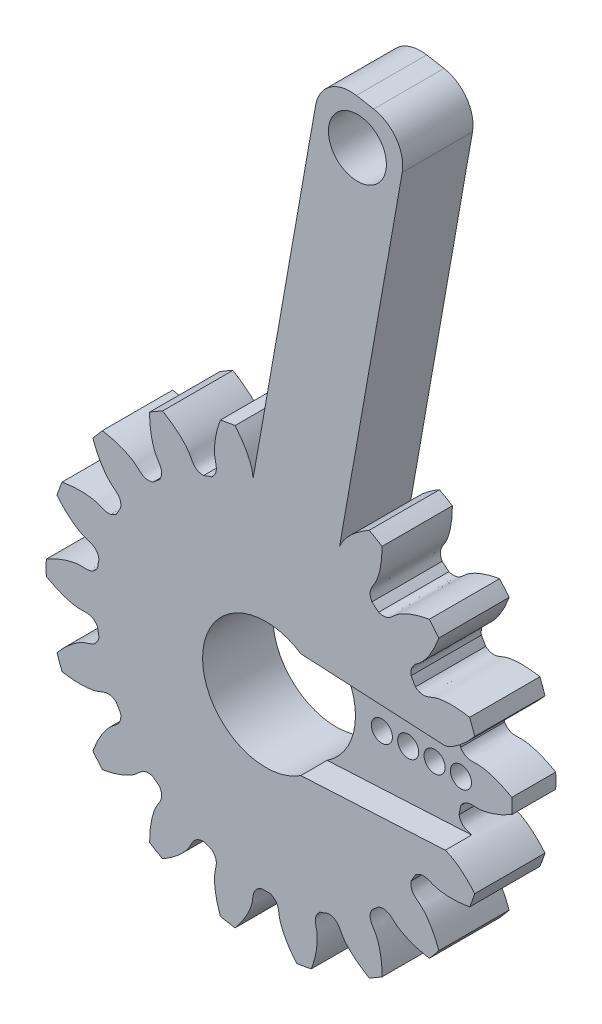
SolidWorks part; units mm, degrees
ref_plane "前视基准面" through (0, 0, 0) normal (0, 0, 1) x (1, 0, 0)
ref_plane "上视基准面" through (0, 0, 0) normal (0, 1, 0) x (1, 0, 0)
ref_plane "右视基准面" through (0, 0, 0) normal (1, 0, 0) x (0, 0, -1)
sketch "草图1" plane through (0, 0, 0) normal (0, 0, 1) x (1, 0, 0)
  circle A0 centre (0, 0) radius 12.5
extrude "凸台-拉伸1" add sketch "草图1" along normal blind 4
ref_axis "基准轴1" through (0, 0, -0.15) along (0, 0, 1)
sketch "草图2" plane through (0, 0, 0) normal (0, 0, 1) x (1, 0, 0)
  line L0 (0, 0) -> (0, 12.5) construction
  circle A0 centre (0, 0) radius 12.5 construction
  arc A1 (0.2493, 9.6843) -> (-0.2493, 9.6843) centre (0, 0) ccw
  arc A2 (3.8732, 14.1333) -> (-3.8732, 14.1333) centre (0, 0) ccw
  spline S0 degree 3 poles (0.2493, 9.6843) (0.7689, 9.8984) (0.7035, 10.2984) (0.7898, 10.6782) (0.7984, 10.7131) (0.8089, 10.7519) (0.8213, 10.7946) (0.8358, 10.841) (0.8526, 10.8911) (0.8718, 10.9449) (0.8935, 11.0022) (0.918, 11.063) (0.9453, 11.1272) (0.9757, 11.1947) (1.0092, 11.2654) (1.046, 11.3392) (1.0863, 11.416) (1.1301, 11.4956) (1.1776, 11.5781) (1.2289, 11.6632) (1.2842, 11.7508) (1.3435, 11.8408) (1.407, 11.9332) (1.4749, 12.0276) (1.5471, 12.1241) (1.6238, 12.2225) (1.7052, 12.3225) (1.7913, 12.4242) (1.8822, 12.5273) (1.978, 12.6316) (2.0788, 12.7371) (2.1846, 12.8436) (2.2956, 12.9508) (2.4118, 13.0587) (2.5334, 13.1671) (2.6602, 13.2757) (2.7925, 13.3845) (2.9303, 13.4932) (3.0735, 13.6017) (3.2224, 13.7099) (3.3768, 13.8174) (3.5926, 13.9613) (3.7594, 14.0654) (3.8732, 14.1333) knots 0 0 0 0 0.187592 0.192996 0.199121 0.205966 0.213531 0.221818 0.230824 0.240552 0.250999 0.262168 0.274057 0.286666 0.299996 0.314047 0.328818 0.344309 0.360521 0.377454 0.395107 0.413481 0.432575 0.45239 0.472926 0.494181 0.516158 0.538855 0.562272 0.58641 0.611269 0.636848 0.663148 0.690168 0.717909 0.74637 0.775552 0.805454 0.836077 0.867421 0.899485 0.932269 1 1 1 1
  spline S1 degree 3 poles (-0.2493, 9.6843) (-0.7689, 9.8984) (-0.7035, 10.2984) (-0.7898, 10.6782) (-0.7984, 10.7131) (-0.8089, 10.7519) (-0.8213, 10.7946) (-0.8358, 10.841) (-0.8526, 10.8911) (-0.8718, 10.9449) (-0.8935, 11.0022) (-0.918, 11.063) (-0.9453, 11.1272) (-0.9757, 11.1947) (-1.0092, 11.2654) (-1.046, 11.3392) (-1.0863, 11.416) (-1.1301, 11.4956) (-1.1776, 11.5781) (-1.2289, 11.6632) (-1.2842, 11.7508) (-1.3435, 11.8408) (-1.407, 11.9332) (-1.4749, 12.0276) (-1.5471, 12.1241) (-1.6238, 12.2225) (-1.7052, 12.3225) (-1.7913, 12.4242) (-1.8822, 12.5273) (-1.978, 12.6316) (-2.0788, 12.7371) (-2.1846, 12.8436) (-2.2956, 12.9508) (-2.4118, 13.0587) (-2.5334, 13.1671) (-2.6602, 13.2757) (-2.7925, 13.3845) (-2.9303, 13.4932) (-3.0735, 13.6017) (-3.2224, 13.7099) (-3.3768, 13.8174) (-3.5926, 13.9613) (-3.7594, 14.0654) (-3.8732, 14.1333) knots 0 0 0 0 0.187592 0.192996 0.199121 0.205966 0.213531 0.221818 0.230824 0.240552 0.250999 0.262168 0.274057 0.286666 0.299996 0.314047 0.328818 0.344309 0.360521 0.377454 0.395107 0.413481 0.432575 0.45239 0.472926 0.494181 0.516158 0.538855 0.562272 0.58641 0.611269 0.636848 0.663148 0.690168 0.717909 0.74637 0.775552 0.805454 0.836077 0.867421 0.899485 0.932269 1 1 1 1
extrude "切除-拉伸1" cut sketch "草图2" along normal through all
pattern_circular "阵列(圆周)1" count 18 over 360 about axis through (0, 0, -0.15) along (0, 0, 1) of "切除-拉伸1"
sketch "草图3" plane through (0, 0, 0) normal (0, 0, 1) x (1, 0, 0)
  circle A0 centre (0, 0) radius 11.25 construction
  dimension "Dn" = 22.5
sketch "草图4" plane through (0, 0, 4) normal (0, 0, 1) x (1, 0, 0)
  circle A0 centre (0, 0) radius 1.65
  dimension "D1" = 3.3
extrude "切除-拉伸2" cut sketch "草图4" against normal blind 10
sketch "草图5" plane through (0, 0, 4) normal (0, 0, 1) x (1, 0, 0)
  line L0 (0, 14.5396) -> (0, -13.6748) construction
  line L1 (0, 14.3969) -> (3.1815, 32.4404)
  line L2 (3.1815, 32.4404) -> (8.1056, 31.5721)
  line L3 (8.1056, 31.5721) -> (4.924, 13.5287)
  line L4 (0, 14.3969) -> (4.924, 13.5287) construction
  line L5 (5.6436, 32.0063) -> (2.462, 13.9628) construction
  line L6 (0, 14.3969) -> (-1.7594, 4.4189)
  line L7 (-1.7594, 4.4189) -> (3.1646, 3.5507)
  line L8 (3.1646, 3.5507) -> (4.924, 13.5287)
  circle A0 centre (5.2094, 29.5442) radius 1.65
  dimension "D5" = 3.3
  dimension "D1" = 10
  dimension "D2" = 5
  dimension "D3" = 30
  dimension "D4" = 2.5
extrude "凸台-拉伸2" add sketch "草图5" against normal up to surface (4 mm away) up to face at (1.65, 0, 0)
fillet "圆角1" radius 2 2 edges at (3.1815, 32.4404, 2) (8.1056, 31.5721, 2)
sketch "草图7" plane through (0, 0, 0) normal (0, 0, -1) x (-1, 0, 0)
  circle A1 centre (0, 0) radius 2.4
  dimension "D1" = 4.8
extrude "切除-拉伸3" cut sketch "草图7" against normal blind 11
sketch "草图8" plane through (0, 0, 0) normal (0, 0, -1) x (-1, 0, 0)
  circle A0 centre (0, 0) radius 3.6
  dimension "D1" = 7.2
extrude "切除-拉伸4" cut sketch "草图8" against normal blind 11
sketch "草图11" plane through (0, 0, 4) normal (0, 0, 1) x (1, 0, 0)
  line L0 (1.99, -3) -> (10.2095, -2.5692)
  line L1 (-0.776, 3) -> (1.99, 3)
  line L2 (-0.776, 3) -> (-0.776, -3)
  line L3 (-0.776, -3) -> (1.99, -3)
  line L4 (16.2969, 3) -> (16.2969, -3)
  line L5 (-0.776, 3) -> (16.2969, -3) construction
  line L6 (-0.776, -3) -> (16.2969, 3) construction
  line L7 (3.0687, 0) -> (13.4274, 0) construction
  line L8 (1.99, 3) -> (10.2095, 2.5692)
  line L9 (10.9859, -3) -> (16.2969, -3)
  line L10 (10.9859, 3) -> (16.2969, 3)
  circle A0 centre (0, 0) radius 3.6 construction
  spline S0 degree 3 poles (871.9004, 1802.4296) (-9.8734, -25.0692) (5.6052, -0.6254) (10.3912, -2.6372) (10.4521, -2.6651) (10.5351, -2.7071) (10.6312, -2.7607) (10.7395, -2.8268) (10.8591, -2.9066) (10.9891, -3.001) (11.1286, -3.1111) (11.2764, -3.2376) (11.4315, -3.3814) (11.5926, -3.5433) (11.7285, -3.6912) (26.9282, -21.2458) (-51.3241, -117.9882) (503.1929, 1934.6625) knots -2.44778 -2.44778 -2.44778 -2.44778 0.187592 0.192996 0.205966 0.221818 0.240552 0.262168 0.286666 0.314047 0.344309 0.377454 0.413481 0.45239 0.494181 0.516158 12.321855 12.321855 12.321855 12.321855 only from (9.4939, -1.9271) to (11.8846, -3.8738) construction
  spline S1 degree 3 poles (10.2095, -2.5692) (10.2562, -2.5846) (10.3127, -2.6042) (10.3912, -2.6372) (10.4521, -2.6651) (10.5351, -2.7071) (10.6312, -2.7607) (10.7395, -2.8268) (10.8598, -2.9071) (10.9425, -2.9672) (10.9859, -3) knots 0.162443 0.162443 0.162443 0.162443 0.187592 0.192996 0.205966 0.221818 0.240552 0.262168 0.286666 0.314458 0.314458 0.314458 0.314458
  spline S2 degree 3 poles (503.2023, -1934.6973) (-51.3249, 117.9893) (26.9283, 21.2459) (11.7285, 3.6912) (11.5926, 3.5433) (11.4315, 3.3814) (11.2764, 3.2376) (11.1286, 3.1111) (10.9891, 3.001) (10.8591, 2.9066) (10.7395, 2.8268) (10.6312, 2.7607) (10.5351, 2.7071) (10.4521, 2.6651) (10.3912, 2.6372) (5.6052, 0.6254) (-9.8733, 25.0691) (871.892, -1802.4122) knots -11.321921 -11.321921 -11.321921 -11.321921 0.483842 0.505819 0.54761 0.586519 0.622546 0.655691 0.685953 0.713334 0.737832 0.759448 0.778182 0.794034 0.807004 0.812408 3.447772 3.447772 3.447772 3.447772 only from (11.8846, 3.8738) to (9.4939, 1.9271) construction
  spline S3 degree 3 poles (10.9859, 3) (10.9425, 2.9672) (10.8598, 2.9071) (10.7395, 2.8268) (10.6312, 2.7607) (10.5351, 2.7071) (10.4521, 2.6651) (10.3912, 2.6372) (10.3127, 2.6042) (10.2562, 2.5846) (10.2095, 2.5692) knots 0.685542 0.685542 0.685542 0.685542 0.713334 0.737832 0.759448 0.778182 0.794034 0.807004 0.812408 0.837557 0.837557 0.837557 0.837557
  point P0 (7.7604, 0)
  dimension "D1" = 6
  dimension "D2" = 3
extrude "切除-拉伸6" cut sketch "草图11" against normal blind 1.5
sketch "草图12" plane through (0, 0, 2.5) normal (0, 0, 1) x (1, 0, 0)
  line L0 (3.6, 0) -> (12.5, 0) construction
  line L1 (5.1, 0) -> (14, 0) construction
  line L2 (6.6, 0) -> (15.5, 0) construction
  arc A0 (1.99, -3) -> (1.99, 3) centre (0, 0) ccw construction
  arc A1 (12.4928, -0.4246) -> (12.4928, 0.4246) centre (0, 0) ccw construction
  circle A2 centre (6.6, 0) radius 0.6
  circle A3 centre (8.1, 0) radius 0.6
  circle A4 centre (9.6, 0) radius 0.6
  circle A5 centre (5.1, 0) radius 0.6
  dimension "D1" = 1.2
  dimension "D3" = 1.2
  dimension "D4" = 1.5
  dimension "D2" = 3
extrude "切除-拉伸7" cut sketch "草图12" against normal blind 11.5
